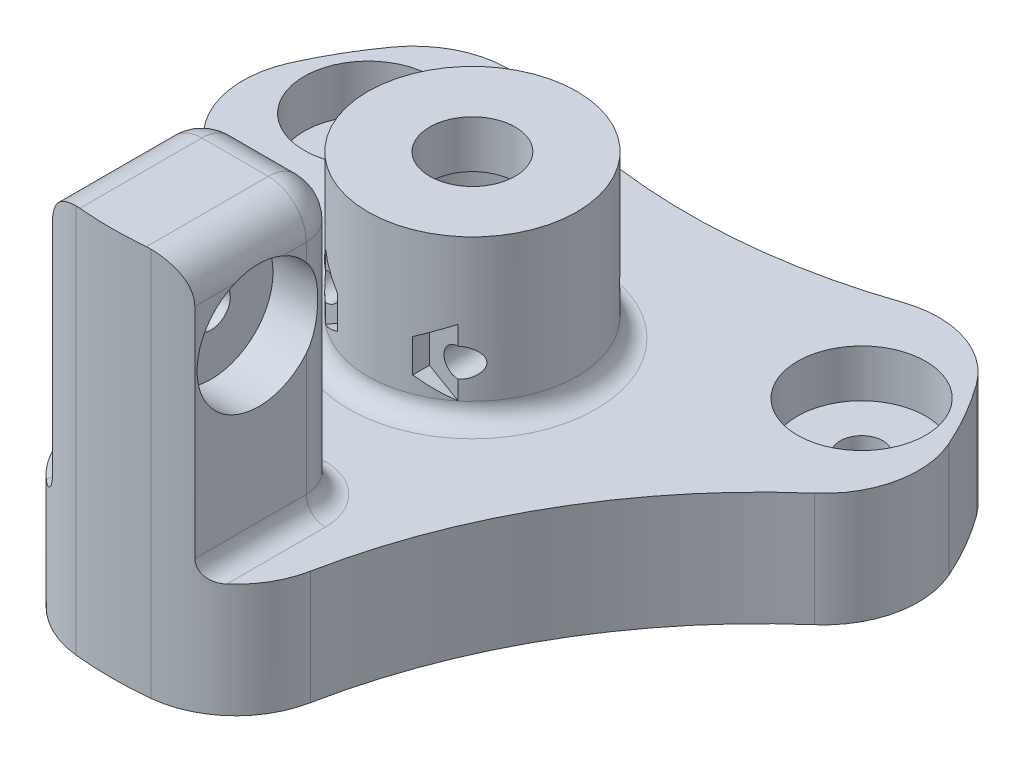
SolidWorks part; units mm, degrees
note: The reader was unsure of these and kept them because the rebuilt part matched: shared geometry of "Sketch1<14>", "Sketch1<16>", "Sketch1<8>", "Sketch1<9>", "Sketch1<10>", "Sketch2<3>", "Sketch3<4>", "Sketch3<5>", "Sketch2<6>".
ref_plane "Front Plane" through (0, 0, 0) normal (0, 0, 1) x (1, 0, 0)
ref_plane "Top Plane" through (0, 0, 0) normal (0, 1, 0) x (1, 0, 0)
ref_plane "Right Plane" through (0, 0, 0) normal (1, 0, 0) x (0, 0, -1)
sketch "Sketch1" plane through (0, 0, 0) normal (0, 1, 0) x (1, 0, 0)
  line L0 (0, 0) -> (-25.9808, 15) construction
  line L1 (-2.125, -33.6806) -> (2.125, -33.6806)
  line L2 (2.125, -33.6806) -> (4.25, -30)
  line L3 (4.25, -30) -> (2.125, -26.3194)
  line L4 (2.125, -26.3194) -> (-2.125, -26.3194)
  line L5 (-2.125, -26.3194) -> (-4.25, -30)
  line L6 (-4.25, -30) -> (-2.125, -33.6806)
  line L7 (0, 0) -> (25.9808, 15) construction
  line L8 (0, 0) -> (0, -30) construction
  circle A0 centre (0, 0) radius 30 construction
  circle A1 centre (0, -30) radius 2.25
  circle A2 centre (-25.9808, 15) radius 2.25
  circle A3 centre (25.9808, 15) radius 2.25
  circle A4 centre (0, 0) radius 8
  circle A6 centre (0, 0) radius 38
  circle A8 centre (0, 0) radius 11
  circle A9 centre (0, 0) radius 4.5
  circle A10 centre (0, -30) radius 4.25 construction
  circle A11 centre (-25.9808, 15) radius 6.75
  circle A12 centre (25.9808, 15) radius 6.75
  point P12 (0, 0)
  dimension "D1" = 3
  dimension "Diametro Base movil " = 60
  dimension "Tornillo 4mm" = 4.5
  dimension "Perforacion Hot end" = 16
  dimension "D3" = 3
  dimension "D4" = 9
  dimension "Diametro tuerca 4mm" = 8.5
  dimension "Diametro Rodamientos 602z" = 13.5
  dimension "D7" = 120
  dimension "Espaciado de base movil" = 8
extrude "Espesor base movil" add sketch "Sketch1" along normal mid plane 12 contours L1 A6 L6 L5 L4 L3 L2 A8 A2 A3 | A8 A4 | L5 L6 L1 L2 L3 L4 A1 | A2 | A3 | A1 | A11 | A12
extrude "Cut-Extrude12" cut sketch "Sketch1<14>" along normal blind 5 from surface at -6 contours A12 | A11 starting at face at (0, -6, 38)
sketch "Sketch1<14>" plane through (0, 0, 0) normal (0, 1, 0) x (1, 0, 0) same geometry as "Sketch1"
extrude "Cut-Extrude14" cut sketch "Sketch1<16>" against normal blind 5 from surface contours A12 | A11
sketch "Sketch1<16>" plane through (0, 0, 0) normal (0, 1, 0) x (1, 0, 0) same geometry as "Sketch1"
extrude "Boss-Extrude2" add sketch "Sketch1<8>" along normal blind 12 from surface at 6 contours A8 | A4 starting at face at (25.9808, 6, -8.25)
sketch "Sketch1<8>" plane through (0, 0, 0) normal (0, 1, 0) x (1, 0, 0) same geometry as "Sketch1"
extrude "Boss-Extrude3" add sketch "Sketch1<9>" along normal blind 5 from surface at 18 contours A8 starting at face at (0, 18, 11)
sketch "Sketch1<9>" plane through (0, 0, 0) normal (0, 1, 0) x (1, 0, 0) same geometry as "Sketch1"
extrude "Cut-Extrude1" cut sketch "Sketch1<10>" against normal through all from surface at 23 contours A9 starting at face at (0, 23, 11)
sketch "Sketch1<10>" plane through (0, 0, 0) normal (0, 1, 0) x (1, 0, 0) same geometry as "Sketch1"
sketch "Sketch2" plane through (0, 0, 0) normal (0, 0, 1) x (1, 0, 0)
  line L0 (0, 0) -> (0, 23) construction
  line L1 (10.0311, 13.25) -> (10.0311, 9.75)
  line L2 (4.5, 23) -> (-4.5, 23) construction
  line L3 (0, 11.5) -> (-7, 11.5) construction
  line L4 (-7, 15) -> (-10.0311, 13.25)
  line L5 (-10.0311, 13.25) -> (-10.0311, 9.75)
  line L6 (-10.0311, 9.75) -> (-7, 8)
  line L7 (-7, 8) -> (-3.9689, 9.75)
  line L8 (-3.9689, 9.75) -> (-3.9689, 13.25)
  line L9 (-3.9689, 13.25) -> (-7, 15)
  line L10 (10.0311, 9.75) -> (7, 8)
  line L11 (7, 8) -> (3.9689, 9.75)
  line L12 (3.9689, 9.75) -> (3.9689, 13.25)
  line L13 (3.9689, 13.25) -> (7, 15)
  line L14 (7, 15) -> (10.0311, 13.25)
  circle A0 centre (-7, 11.5) radius 1.5
  circle A1 centre (-7, 11.5) radius 4
  circle A2 centre (7, 11.5) radius 4
  circle A3 centre (7, 11.5) radius 1.5
  circle A4 centre (-7, 11.5) radius 3.5 construction
  dimension "Tornillo 3mm" = 3
  dimension "Cabeza tornillo 3mm" = 8
  dimension "Tuerca 6mm" = 7
  dimension "D1" = 7
extrude "Cut-Extrude4" cut sketch "Sketch2<3>" against normal through all from offset 8.5 contours L14 L13 L12 L11 L10 L1 A3 | A2 L13 L14 L1 L10 L11 L12 | A1 L9 L8 L7 L6 L5 L4 | A0 offset against normal yes
sketch "Sketch2<3>" plane through (0, 0, 0) normal (0, 0, 1) x (1, 0, 0) same geometry as "Sketch2"
extrude "Cut-Extrude5" cut sketch "Sketch2" along normal blind 7 from offset 8.5 contours L9 L4 L5 L6 L7 L8 | L14 L1 L10 L11 L12 L13
sketch "Sketch3" plane through (0, 0, 0) normal (1, 0, 0) x (0, 0, -1)
  line L0 (-22.75, 6) -> (-27.25, 6) construction
  line L2 (-39, 6) -> (-39, 35)
  line L3 (-39, 35) -> (-25, 35)
  line L4 (-21, 31) -> (-21, 6)
  line L5 (-21, 6) -> (-39, 6)
  line L6 (-30, 33) -> (-30, 6) construction
  line L7 (-15.9999, 25) -> (-39, 25) construction
  line L8 (38, 6) -> (-38, 6) construction
  circle A0 centre (-30, 25) radius 6.5
  circle A3 centre (-30, 25) radius 2
  arc A4 (-25, 35) -> (-21, 31) centre (-25, 31) cw
  dimension "D3" = 13
  dimension "D5" = 4
  dimension "D1" = 4
  dimension "D2" = 18
  dimension "D4" = 10
  dimension "D6" = 29
  dimension "D7" = 30
  dimension "D8" = 19
extrude "Boss-Extrude4" add sketch "Sketch3" along normal mid plane 15
extrude "Cut-Extrude15" cut sketch "Sketch3<4>" along normal blind 5 from surface at -7.5 contours A0 starting at face at (-7.5, 25, 28)
sketch "Sketch3<4>" plane through (0, 0, 0) normal (1, 0, 0) x (0, 0, -1) same geometry as "Sketch3"
extrude "Cut-Extrude16" cut sketch "Sketch3<5>" against normal blind 5 from surface at 7.5 contours A0 starting at face at (7.5, 25, 28)
sketch "Sketch3<5>" plane through (0, 0, 0) normal (1, 0, 0) x (0, 0, -1) same geometry as "Sketch3"
sketch "Sketch4" plane through (0, -6, 0) normal (0, -1, 0) x (1, 0, 0)
  line L0 (7.5, 37.2525) -> (7.5, 39)
  line L1 (7.5, 39) -> (-7.5, 39)
  line L2 (-7.5, 39) -> (-7.5, 37.2525)
  arc A0 (7.5, 37.2525) -> (-7.5, 37.2525) centre (0, 0) ccw construction
  arc A1 (7.5, 37.2525) -> (-7.5, 37.2525) centre (0, 0) ccw
extrude "Cut-Extrude17" cut sketch "Sketch4" against normal through all
fillet "Fillet3" radius 4 6 edges at (-7.5, 35, 31.1263) (7.5, 35, 31.1263) (-7.5, 18.5, 21) (7.5, 18.5, 21) (-7.5, 33.8284, 22.1716) (7.5, 33.8284, 22.1716)
sketch "Sketch5" plane through (0, -6, 0) normal (0, -1, 0) x (1, 0, 0)
  circle A0 centre (0, 0) radius 11.25
  dimension "D1" = 22.5
extrude "Cut-Extrude18" cut sketch "Sketch5" against normal blind 4
fillet "Fillet5" radius 1 1 edges at (0, 18, 8)
extrude "Cut-Extrude19" cut sketch "Sketch2<6>" against normal blind 10 and the other way blind 10 contours A3 | A0
sketch "Sketch2<6>" plane through (0, 0, 0) normal (0, 0, 1) x (1, 0, 0) same geometry as "Sketch2"
fillet "Fillet6" radius 2 6 edges at (7.5, 6, 31.1263) (6.3284, 6, 22.1716) (0, 6, 21) (-6.3284, 6, 22.1716) (-7.5, 6, 31.1263) (0, 6, 11)
sketch "Sketch6" plane through (0, 6, 0) normal (0, 1, 0) x (1, 0, 0)
  line L0 (0, 0) -> (0, -30) construction
  arc A4 (-21.5013, 26.6698) -> (-33.8474, 5.2858) centre (-25.9808, 15) ccw
  arc A5 (33.8474, 5.2858) -> (21.5013, 26.6698) centre (25.9808, 15) ccw
  arc A6 (-12.3461, -31.9556) -> (12.3461, -31.9556) centre (0, -30) ccw
  arc A7 (-12.3461, -31.9556) -> (-33.8474, 5.2858) centre (-71.6073, -41.3425) ccw
  arc A8 (33.8474, 5.2858) -> (12.3461, -31.9556) centre (71.6073, -41.3425) ccw
  arc A10 (-21.5013, 26.6698) -> (21.5013, 26.6698) centre (0, 82.6849) ccw
  circle A11 centre (0, 0) radius 49.8972
  dimension "D1" = 30
  dimension "D2" = 120
  dimension "D3" = 25
extrude "Cut-Extrude20" cut sketch "Sketch6" against normal through all
fillet "Fillet8" radius 10 6 edges at (-10.6998, 0, 36.4625) (10.6998, 0, 36.4625) (-26.2275, 0, -27.4976) (-36.9274, 0, -8.9649) (36.9274, 0, -8.9649) (26.2275, 0, -27.4976)
